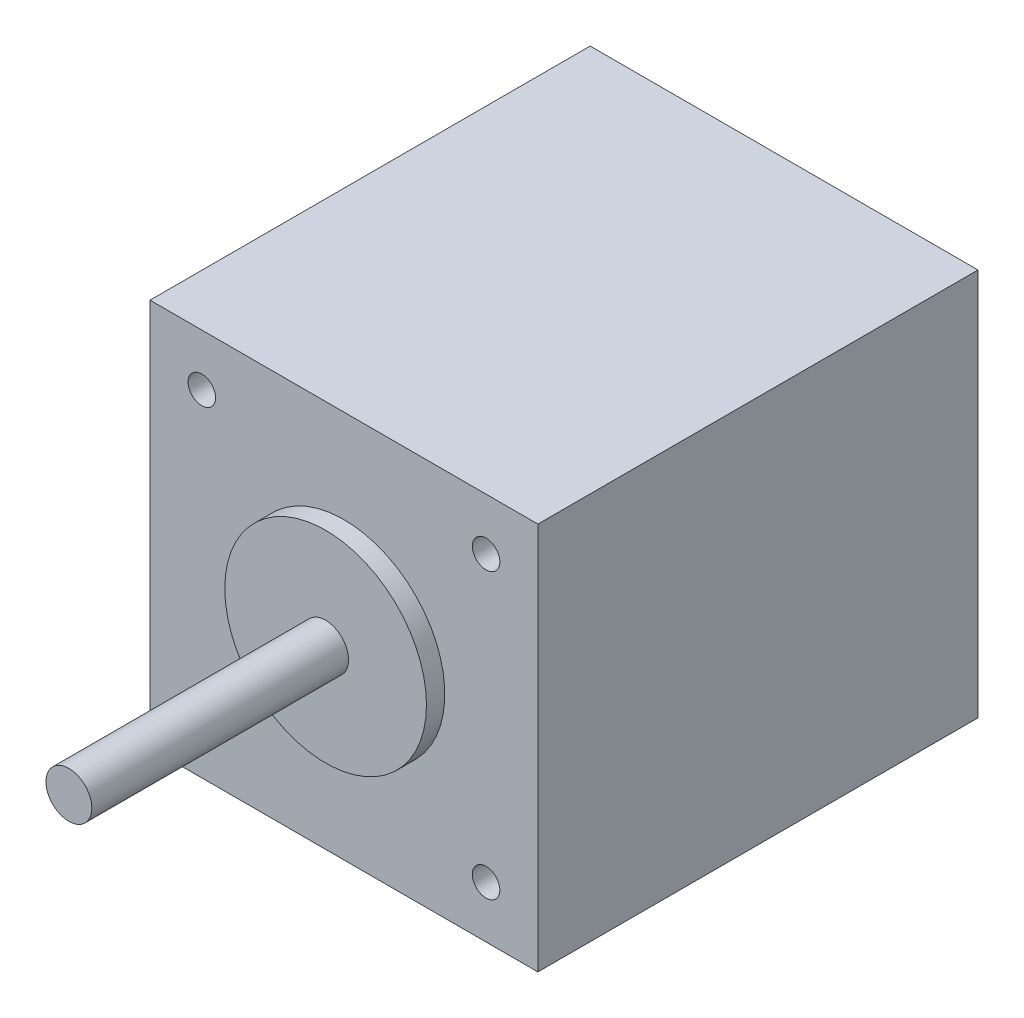
SolidWorks part; units mm, degrees
ref_plane "Спереди" through (0, 0, 0) normal (0, 0, 1) x (1, 0, 0)
ref_plane "Сверху" through (0, 0, 0) normal (0, 1, 0) x (1, 0, 0)
ref_plane "Справа" through (0, 0, 0) normal (1, 0, 0) x (0, 0, -1)
other "Configuration Table"
sketch "Эскиз1" plane through (0, 0, 0) normal (0, 0, 1) x (1, 0, 0)
  line L1 (-21.15, -21.15) -> (21.15, -21.15)
  line L2 (-21.15, -21.15) -> (-21.15, 21.15)
  line L3 (-21.15, 21.15) -> (21.15, 21.15)
  line L4 (21.15, -21.15) -> (21.15, 21.15)
  line L5 (-21.15, -21.15) -> (21.15, 21.15) construction
  line L6 (-21.15, 21.15) -> (21.15, -21.15) construction
  point P0 (0, 0)
  dimension "D1" = 42.3
  dimension "D2" = 42.3
extrude "Корпус" add sketch "Эскиз1" along normal blind 48
sketch "Эскиз2" plane through (0, 0, 0) normal (0, 0, 1) x (1, 0, 0)
  circle A0 centre (0, 0) radius 2.5
extrude "Вал_ПРЕДВ" add sketch "Эскиз2" along normal blind 78
sketch "Эскиз3" plane through (0, 0, 0) normal (0, 0, 1) x (1, 0, 0)
  circle A0 centre (0, 0) radius 11
  dimension "D1" = 22
extrude "Буртик_ПРЕДВ" add sketch "Эскиз3" along normal blind 50
sketch "Эскиз4" plane through (0, 0, 0) normal (0, 0, 1) x (1, 0, 0)
  circle A0 centre (0, 0) radius 8
  dimension "D1" = 16
sketch "Эскиз5" plane through (0, 0, 0) normal (0, 0, 1) x (1, 0, 0)
  circle A0 centre (-15.5, -15.5) radius 1.5
  circle A1 centre (-15.5, 15.5) radius 1.5
  circle A2 centre (15.5, -15.5) radius 1.5
  circle A3 centre (15.5, 15.5) radius 1.5
  dimension "D2" = 3
  dimension "D3" = 3
  dimension "D4" = 3
extrude "Крепеж_М3_ПРЕДВ" cut sketch "Эскиз5" against normal blind 4.5 from offset 48
equation "\"Мотор X ширина корпуса\"= 42.3"
equation "\"Мотор X высота корпуса\"= 42.3"
equation "\"Мотор X длина корпуса\"= 40"
equation "\"Мотор X вылет вала\"= 19.8"
equation "\"Мотор Y ширина корпуса\"= 42.3"
equation "\"Мотор Y высота корпуса\"= 42.3"
equation "\"Мотор Y длина корпуса\"= 48"
equation "\"Мотор Y вылет вала\"= 30"
equation "\"Мотор Z ширина корпуса\"= 42"
equation "\"Мотор Z высота корпуса\"= 42"
equation "\"Мотор Z длина корпуса\"= 40"
equation "\"Мотор Z вылет вала\"= 23"
equation "\"Мотор диаметр вала ПРЕДВ\"= 5"
equation "\"Мотор шаг крепления ПРЕДВ\"= 31"
equation "\"Мотор диаметр отверстий ПРЕДВ\"= 3"
equation "\"Мотор глубина отверстий ПРЕДВ\"= 4.5"
equation "\"Мотор диаметр буртика ПРЕДВ\"= 22"
equation "\"Мотор высота буртика ПРЕДВ\"= 2"
equation "\"Мотор диаметр шкива ПРЕДВ\"= 16"
equation "\"Мотор длина шкива ПРЕДВ\"= 12"
equation "\"Мотор отступ шкива ПРЕДВ\"= 5"
equation "\"Мотор X шаг градусов\"= 1.8"
equation "\"Мотор Y шаг градусов\"= 1.8"
equation "\"Мотор Z шаг градусов\"= 1.8"
equation "\"Мотор Y диаметр ротора\"= 25.78"
equation "\"D1@Эскиз1\" = \"Мотор Y ширина корпуса\""
equation "\"D1@Корпус\" = \"Мотор Y длина корпуса\""
equation "\"D1@Эскиз2\" = \"Мотор диаметр вала ПРЕДВ\""
equation "\"D1@Вал_ПРЕДВ\" = \"Мотор Y длина корпуса\" + \"Мотор Y вылет вала\""
equation "\"D1@Эскиз3\" = \"Мотор диаметр буртика ПРЕДВ\""
equation "\"D1@Буртик_ПРЕДВ\" = \"Мотор Y длина корпуса\" + \"Мотор высота буртика ПРЕДВ\""
equation "\"D1@Эскиз4\" = \"Мотор диаметр шкива ПРЕДВ\""
equation "\"D1@Эскиз5\" = \"Мотор диаметр отверстий ПРЕДВ\""
equation "\"D2@Эскиз5\" = \"Мотор диаметр отверстий ПРЕДВ\""
equation "\"D3@Эскиз5\" = \"Мотор диаметр отверстий ПРЕДВ\""
equation "\"D4@Эскиз5\" = \"Мотор диаметр отверстий ПРЕДВ\""
equation "\"D1@Крепеж_М3_ПРЕДВ\" = \"Мотор глубина отверстий ПРЕДВ\""
equation "\"D19@Крепеж_М3_ПРЕДВ\" = \"Мотор Y длина корпуса\""
equation "\"Ширина груза\"= 420"
equation "\"Глубина груза\"= 490"
equation "\"Высота груза\"= 297"
equation "\"Ширина ячейки\"= \"Ширина груза\" + 10"
equation "\"Глубина ячейки\"= \"Глубина груза\" + 10"
equation "\"Высота ячейки\"= \"Высота груза\" + 10 + 13"
equation "\"Колво ячеек ширина\"= 2"
equation "\"Колво ячеек высота\"= 2"
equation "\"Толщина стенки\" = 6"
equation "\"Крепление дверцы\"= 5"
equation "\"Ширина рейки\"= \"Толщина шестерни\""
equation "\"Высота рейки\"= 20"
equation "\"Высота пола\"= 20"
equation "\"Колво полозьев\"= 5"
equation "\"Отступ рейки\"= 20"
equation "\"Глубина каретки\"= \"Глубина ячейки\" + 30 + \"Мотор Y высота корпуса\" + 20"
equation "\"Отступ шпильки\"= 26"
equation "\"Диаметр шпильки\"= 5"
equation "\"Длинна шпильки\"= ( \"Высота ячейки\" + \"Толщина стенки\" + \"Высота пола\" ) * \"Колво ячеек высота\" + ( \"Толщина стенки\" + \"Отступ рейки\" ) * 2 "
equation "\"Ширина пластины\"= 50  "
equation "\"Высота зона выгрузки\"= \"Высота ячейки\" * 2 + \"Толщина стенки\" * 2"
equation "\"Колво выгрузки\"= 1"
equation "\"Отступ крепления мотора фиксации\" = 30"
equation "\"Ширина ячейки выгрузки\"= \"Ширина ячейки\" + \"Толщина стенки\" + \"Отступ крепления мотора фиксации\"*2"
equation "\"Длинна рейки\"= ( \"Ширина ячейки\" + \"Толщина стенки\" + \"Крепление дверцы\" ) * \"Колво ячеек ширина\" + \"Ширина ячейки выгрузки\" * \"Колво выгрузки\" + \"Толщина стенки\""
equation "\"Толщина шестерни\"= 10"
